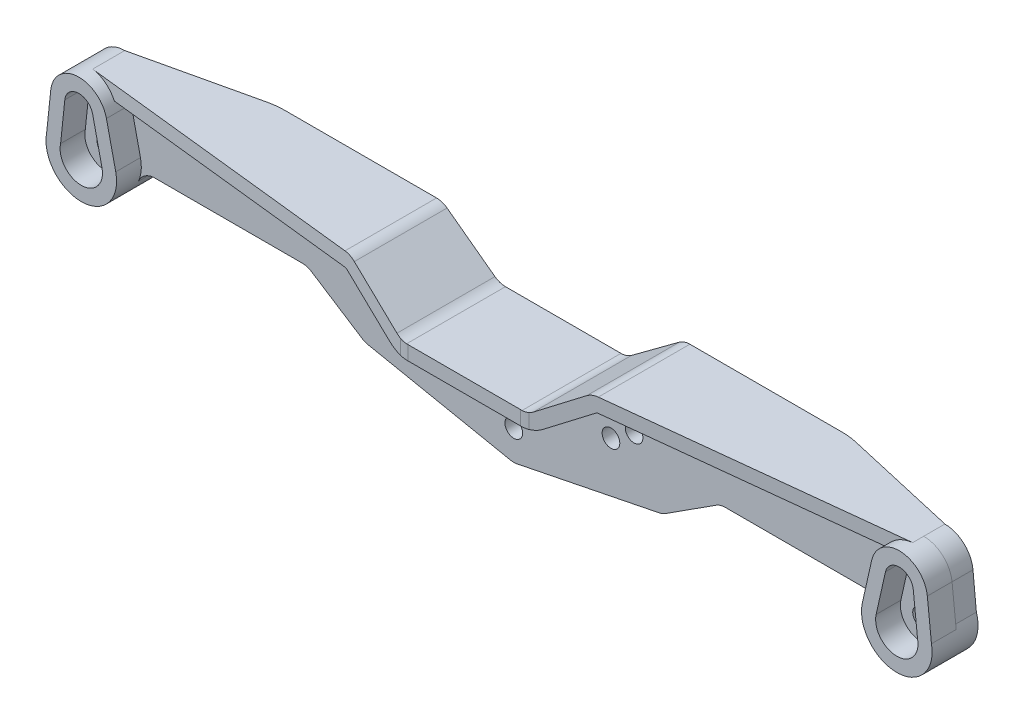
SolidWorks part; units mm, degrees
ref_plane "Front Plane" through (0, 0, 0) normal (0, 0, 1) x (1, 0, 0)
ref_plane "Top Plane" through (0, 0, 0) normal (0, 1, 0) x (1, 0, 0)
ref_plane "Right Plane" through (0, 0, 0) normal (1, 0, 0) x (0, 0, -1)
sketch "Sketch3" plane through (0, 0, 0) normal (0, 0, 1) x (1, 0, 0)
  line L0 (-58.0676, 9.1299) -> (-17.9277, 9.1299)
  line L1 (-16.4399, 8.639) -> (-9.6629, 3.6207)
  line L2 (-62.0442, 5.5617) -> (-62.6952, -0.4332)
  line L3 (20.6174, -6.7133) -> (0.4941, -10.7705)
  line L4 (28.6186, -1.7679) -> (21.4763, -6.3649)
  line L5 (-50.8066, -1.3701) -> (-29.9716, -1.3701)
  line L6 (-28.6186, -1.7679) -> (-21.4763, -6.3649)
  line L7 (-20.6174, -6.7133) -> (-0.4941, -10.7705)
  line L8 (-8.1752, 3.1299) -> (8.1752, 3.1299)
  line L9 (50.8066, -1.3701) -> (29.9716, -1.3701)
  line L10 (62.0062, 5.5147) -> (62.4857, 0.5536)
  line L11 (16.4399, 8.639) -> (9.6629, 3.6207)
  line L12 (0, 3.1299) -> (0, -6.6201) construction
  line L13 (-20.3031, 3.614) -> (-13.7583, -0.973) construction
  line L14 (0, -5.3701) -> (5.8477, -5.3701) construction
  line L15 (58.0247, 9.1299) -> (17.9277, 9.1299)
  circle A0 centre (0, -6.6201) radius 1.25
  circle A1 centre (-57.7244, -0.973) radius 1.25
  arc A2 (-62.6952, -0.4332) -> (-53.1125, -2.9044) centre (-57.7244, -0.973) ccw
  arc A3 (62.4857, 0.5536) -> (53.1125, -2.9044) centre (57.7244, -0.973) cw
  circle A4 centre (57.7244, -0.973) radius 1.25
  circle A5 centre (-20.3031, 3.614) radius 1.25
  circle A6 centre (-17.0307, 1.3205) radius 1.25
  circle A7 centre (-13.7583, -0.973) radius 1.25
  circle A8 centre (13.7583, -0.973) radius 1.25
  circle A9 centre (17.0307, 1.3205) radius 1.25
  circle A10 centre (20.3031, 3.614) radius 1.25
  arc A11 (62.0062, 5.5147) -> (58.0247, 9.1299) centre (58.0247, 5.1299) ccw
  arc A12 (-58.0676, 9.1299) -> (-62.0442, 5.5617) centre (-58.0676, 5.1299) ccw
  arc A13 (-9.6629, 3.6207) -> (-8.1752, 3.1299) centre (-8.1752, 5.6299) ccw
  arc A14 (8.1752, 3.1299) -> (9.6629, 3.6207) centre (8.1752, 5.6299) ccw
  arc A15 (17.9277, 9.1299) -> (16.4399, 8.639) centre (17.9277, 6.6299) ccw
  arc A16 (-17.9277, 9.1299) -> (-16.4399, 8.639) centre (-17.9277, 6.6299) cw
  arc A17 (29.9716, -1.3701) -> (28.6186, -1.7679) centre (29.9716, -3.8701) ccw
  arc A18 (21.4763, -6.3649) -> (20.6174, -6.7133) centre (20.1233, -4.2627) cw
  arc A19 (0.4941, -10.7705) -> (-0.4941, -10.7705) centre (0, -8.3198) cw
  arc A20 (-20.6174, -6.7133) -> (-21.4763, -6.3649) centre (-20.1233, -4.2627) cw
  arc A21 (-28.6186, -1.7679) -> (-29.9716, -1.3701) centre (-29.9716, -3.8701) ccw
  arc A22 (53.1125, -2.9044) -> (50.8066, -1.3701) centre (50.8066, -3.8701) ccw
  arc A23 (-50.8066, -1.3701) -> (-53.1125, -2.9044) centre (-50.8066, -3.8701) ccw
  point P17 (0, 0)
  point P29 (61.6568, 9.1299)
  point P33 (-61.6568, 9.1299)
  point P34 (2.9239, -5.3701)
  point P44 (-9, 3.1299)
  point P49 (9, 3.1299)
  point P52 (17.1028, 9.1299)
  point P56 (-17.1028, 9.1299)
  point P59 (29.2366, -1.3701)
  point P62 (21.0797, -6.6201)
  point P65 (0, -10.8701)
  point P68 (-21.0797, -6.6201)
  point P71 (-29.2366, -1.3701)
  point P74 (52.7402, -1.3701)
  point P77 (-52.7402, -1.3701)
  dimension "D5" = 2.5
  dimension "D2" = 2.5
  dimension "D8" = 5
  dimension "D14" = 2.5
  dimension "D15" = 2.5
  dimension "D16" = 2.5
  dimension "D17" = 4
  dimension "D18" = 2.5
  dimension "D3" = 18
  dimension "D4" = 6
  dimension "D6" = 8.5
  dimension "D7" = 58
  dimension "D9" = 3.1798
  dimension "D10" = 6.6201
  dimension "D11" = 14
  dimension "D12" = 10.5
  dimension "D13" = 96.197
extrude "Boss-Extrude2" add sketch "Sketch3" along normal blind 3 separate body
sketch "Sketch5" plane through (0, 0, 3) normal (0, 0, 1) x (1, 0, 0)
  line L25 (58.0247, 7.1299) -> (17.9277, 7.1299)
  line L26 (17.6301, 7.0317) -> (10.8531, 2.0134)
  line L27 (8.1752, 1.1299) -> (-8.1752, 1.1299)
  line L28 (-10.8531, 2.0134) -> (-17.6301, 7.0317)
  line L29 (-17.9277, 7.1299) -> (-58.0676, 7.1299)
  line L30 (58.0247, 9.1299) -> (17.9277, 9.1299)
  line L31 (16.4399, 8.639) -> (9.6629, 3.6207)
  line L32 (8.1752, 3.1299) -> (-8.1752, 3.1299)
  line L33 (-9.6629, 3.6207) -> (-16.4399, 8.639)
  line L34 (-17.9277, 9.1299) -> (-58.0676, 9.1299)
  line L35 (58.0247, 9.1299) -> (17.9277, 9.1299)
  line L36 (16.4399, 8.639) -> (9.6629, 3.6207)
  line L37 (8.1752, 3.1299) -> (-8.1752, 3.1299)
  line L38 (-9.6629, 3.6207) -> (-16.4399, 8.639)
  line L39 (-17.9277, 9.1299) -> (-58.0676, 9.1299)
  line L40 (-58.0676, 9.1299) -> (-58.0676, 7.1299)
  line L41 (-58.0676, 7.1299) -> (-58.2669, 6.7547)
  line L42 (58.0247, 9.1299) -> (58.0247, 7.1299)
  arc A20 (17.9277, 7.1299) -> (17.6301, 7.0317) centre (17.9277, 6.6299) ccw
  arc A21 (8.1752, 1.1299) -> (10.8531, 2.0134) centre (8.1752, 5.6299) ccw
  arc A22 (-10.8531, 2.0134) -> (-8.1752, 1.1299) centre (-8.1752, 5.6299) ccw
  arc A23 (-17.6301, 7.0317) -> (-17.9277, 7.1299) centre (-17.9277, 6.6299) ccw
  arc A24 (17.9277, 9.1299) -> (16.4399, 8.639) centre (17.9277, 6.6299) ccw
  arc A25 (8.1752, 3.1299) -> (9.6629, 3.6207) centre (8.1752, 5.6299) ccw
  arc A26 (-9.6629, 3.6207) -> (-8.1752, 3.1299) centre (-8.1752, 5.6299) ccw
  arc A27 (-16.4399, 8.639) -> (-17.9277, 9.1299) centre (-17.9277, 6.6299) ccw
  arc A28 (17.9277, 9.1299) -> (16.4399, 8.639) centre (17.9277, 6.6299) ccw
  arc A29 (8.1752, 3.1299) -> (9.6629, 3.6207) centre (8.1752, 5.6299) ccw
  arc A30 (-9.6629, 3.6207) -> (-8.1752, 3.1299) centre (-8.1752, 5.6299) ccw
  arc A31 (-16.4399, 8.639) -> (-17.9277, 9.1299) centre (-17.9277, 6.6299) ccw
  line M15 (58.0247, 9.1299) -> (17.9277, 9.1299)
  arc M16 (17.9277, 9.1299) -> (16.4399, 8.639) centre (17.9277, 6.6299) ccw
  line M17 (16.4399, 8.639) -> (9.6629, 3.6207)
  arc M18 (9.6629, 3.6207) -> (8.1752, 3.1299) centre (8.1752, 5.6299) cw
  line M19 (8.1752, 3.1299) -> (-8.1752, 3.1299)
  arc M20 (-8.1752, 3.1299) -> (-9.6629, 3.6207) centre (-8.1752, 5.6299) cw
  line M21 (-9.6629, 3.6207) -> (-16.4399, 8.639)
  arc M22 (-16.4399, 8.639) -> (-17.9277, 9.1299) centre (-17.9277, 6.6299) ccw
  line M23 (-17.9277, 9.1299) -> (-58.0676, 9.1299)
  dimension "D1" = 0
  dimension "D2" = 2
extrude "Boss-Extrude3" add sketch "Sketch5" along normal blind 7 and the other way blind 7 contours A23 L28 A22 L27 A21 L26 A20 L25 L42 L40 L29 M15 M16 M17 M18 M19 M20 M21 M22 M23 region at (37.9762, 8.2935, 3)
sketch "Sketch6" plane through (0, 9.1299, 0) normal (0, 1, 0) x (1, 0, 0)
  line L0 (-58.0676, 0) -> (-41.6675, 3.7486)
  line L1 (-17.9277, 4) -> (-58.0676, 4) construction
  line L2 (-39.4393, 4) -> (0, 4)
  line L3 (8.1752, 4) -> (-8.1752, 4) construction
  line L4 (-40.5676, 4) -> (-31.0563, 4)
  line L5 (-39.4393, 4) -> (-58.0676, 4)
  line L6 (-58.0676, 4) -> (-58.0676, 0)
  line L7 (-58.0676, -4.5466) -> (-9.0763, -9.9399)
  line L8 (-58.0676, -3) -> (-58.0676, -10) construction
  line L9 (-9.6629, -10) -> (-8.1752, -10) construction
  line L10 (-7.9821, -10) -> (-5.3351, -10)
  line L11 (8.1752, -10) -> (-8.1752, -10) construction
  line L12 (-58.0676, -10) -> (-58.0676, -4.5466)
  line L13 (0, 0) -> (0, -5.2785) construction
  line L14 (58.0676, -10) -> (58.0676, -4.5466)
  line L15 (7.9821, -10) -> (5.3351, -10)
  line L16 (58.0676, -4.5466) -> (9.0763, -9.9399)
  line L17 (58.0676, 4) -> (58.0676, 0)
  line L18 (39.4393, 4) -> (58.0676, 4)
  line L19 (40.5676, 4) -> (31.0563, 4)
  line L20 (58.0676, 0) -> (41.6675, 3.7486)
  line L21 (-58.0676, -10) -> (-7.9821, -10)
  line L22 (7.9821, -10) -> (58.0676, -10)
  arc A0 (-41.6675, 3.7486) -> (-39.4393, 4) centre (-39.4393, -6) cw
  arc A1 (-7.9821, -10) -> (-9.0763, -9.9399) centre (-7.9821, 0) cw
  arc A2 (7.9821, -10) -> (9.0763, -9.9399) centre (7.9821, 0) ccw
  arc A3 (41.6675, 3.7486) -> (39.4393, 4) centre (39.4393, -6) ccw
  point P25 (-8.5308, -10)
  point P44 (8.5308, -10)
  line M3 (-17.9277, -10) -> (-17.9277, 4)
  line M4 (-17.9277, 4) -> (-58.0676, 4)
  line M5 (-58.0676, 4) -> (-58.0676, 0)
  line M7 (-58.0676, -3) -> (-58.0676, -10)
  line M8 (-58.0676, -10) -> (-17.9277, -10)
  dimension "D2" = 10
  dimension "D3" = 10
  dimension "D1" = 17.5
extrude "Cut-Extrude1" cut sketch "Sketch6" against normal through all contours L0 A0 M4 M5 | L7 M7 M8 M3 | A3 L20 L17 L18 | A2 L22 L14 L16 | L21 L12 L7 A1 region at (-52.2184, 9.1299, -2.6684) region at (-42.5542, 9.1299, 8.1272) region at (41.554, 9.1299, 8.1823) region at (52.2184, 9.1299, -2.6684)
sketch "Sketch7" plane through (0, 0, 3) normal (0, 0, 1) x (1, 0, 0)
  line L0 (-62.6288, 0) -> (-62.0442, 5.5617)
  line L1 (-54.1645, 6.0048) -> (-52.8455, 0.1207)
  line L2 (-56.116, 5.5673) -> (-54.7971, -0.3168)
  line L3 (-60.6506, -0.3113) -> (-60.0556, 5.3486)
  arc A0 (-62.6288, 0) -> (-52.8455, 0.1207) centre (-57.7244, -0.973) ccw
  arc A1 (-62.6952, -0.4332) -> (-53.1125, -2.9044) centre (-57.7244, -0.973) ccw construction
  arc A2 (-62.0442, 5.5617) -> (-54.1645, 6.0048) centre (-58.0676, 5.1299) cw
  arc A3 (-58.0676, 9.1299) -> (-62.0442, 5.5617) centre (-58.0676, 5.1299) ccw construction
  arc A4 (-60.0556, 5.3486) -> (-56.116, 5.5673) centre (-58.0676, 5.1299) cw
  arc A5 (-60.6506, -0.3113) -> (-54.7971, -0.3168) centre (-57.7244, -0.973) ccw
  dimension "D1" = 2
extrude "Boss-Extrude4" add sketch "Sketch7" along normal blind 3.5
mirror "Mirror1" about plane through (0, 0, 0) normal (1, 0, 0) of "Boss-Extrude4"
sketch "Sketch8" plane through (0, 0, -4) normal (0, 0, -1) x (-1, 0, 0)
  line L0 (-23.819, 3.614) -> (-24.839, 3.614)
  line L1 (-24.839, 3.614) -> (-24.839, 7.1299)
  line L2 (-58.0247, 7.1299) -> (-17.9277, 7.1299) construction
  line L3 (-24.839, 7.1299) -> (-20.3031, 7.1299)
  line L4 (0, 0) -> (0, -2.7665) construction
  line L5 (24.839, 7.1299) -> (20.3031, 7.1299)
  line L6 (24.839, 3.614) -> (24.839, 7.1299)
  line L7 (23.819, 3.614) -> (24.839, 3.614)
  arc A0 (-20.3031, 7.1299) -> (-23.819, 3.614) centre (-20.3031, 3.614) ccw
  arc A1 (20.3031, 7.1299) -> (23.819, 3.614) centre (20.3031, 3.614) cw
extrude "Boss-Extrude5" add sketch "Sketch8" against normal up to surface (4 mm away) up to face at (56.4744, -0.973, 0)
